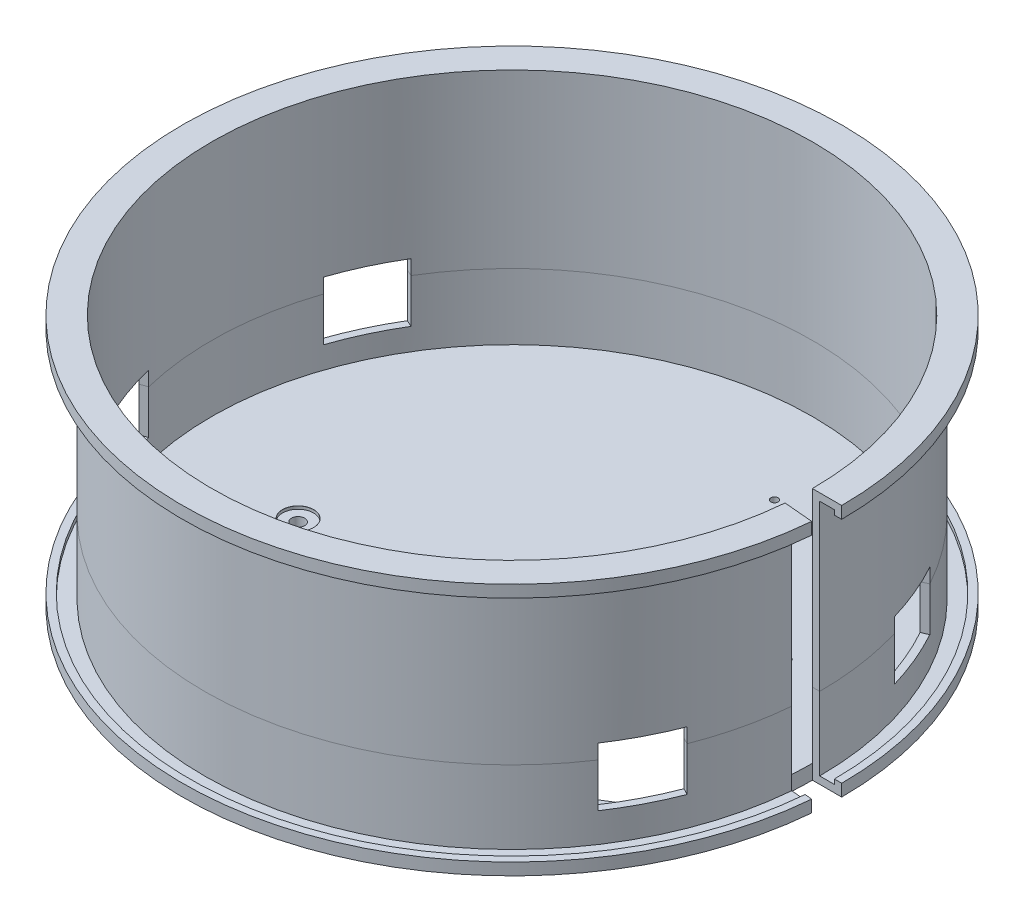
SolidWorks part; units mm, degrees
ref_plane "Front Plane" through (0, 0, 0) normal (0, 0, 1) x (1, 0, 0)
ref_plane "Top Plane" through (0, 0, 0) normal (0, 1, 0) x (1, 0, 0)
ref_plane "Right Plane" through (0, 0, 0) normal (1, 0, 0) x (0, 0, -1)
ref_axis "Axis1" through (0, 90.51, 0) along (0, -1, 0)
sketch "Sketch2" plane through (0, 0, 0) normal (0, 1, 0) x (1, 0, 0)
  circle A0 centre (0, 0) radius 102.5
  dimension "D1" = 102.5
extrude "Boss-Extrude1" add sketch "Sketch2" along normal blind 5
sketch "Sketch1" plane through (0, 0, 0) normal (0, 0, 1) x (1, 0, 0)
  line L0 (0, 82.2536) -> (0, -82.7575) construction
  line L1 (105, 2.5) -> (110, 2.5)
  line L2 (102.5, 0) -> (112.5, 0)
  line L3 (102.5, 0) -> (102.5, 86.2)
  line L4 (102.5, 86.2) -> (112.5, 86.2)
  line L5 (112.5, 0) -> (112.5, 86.2)
  line L6 (110, 2.5) -> (110, 83.7)
  line L7 (105, 83.7) -> (110, 83.7)
  line L8 (105, 2.5) -> (105, 83.7)
  line L9 (110, 82.1) -> (112.5, 82.1)
  line L10 (110, 4.1) -> (112.5, 4.1)
  line L11 (102.5, 43.1) -> (112.5, 43.1) construction
  dimension "D2" = 5
  dimension "D3" = 81.2
  dimension "D4" = 1.6
  dimension "D1" = 2.5
revolve "Revolve1" add sketch "Sketch1" angle 177.5 about L0 region at (104.6983, 43.1, 0) reverse direction yes
sketch "Sketch3" plane through (0, 0, 0) normal (0, 1, 0) x (1, 0, 0)
  line L0 (0, 0) -> (130, 0) construction
  line L1 (0, 0) -> (-119.4763, 5.2164) construction
  line L2 (-96.7219, 33.9283) -> (-88.2921, 52.0649)
  line L3 (90.32, 48.4619) -> (98.0115, 30)
  line L4 (0, 0) -> (92.9211, 90.9157) construction
  line L5 (0, 0) -> (2.8359, 129.9691) construction
  line L6 (0, 0) -> (-88.867, 94.8823) construction
  line L7 (0, 0) -> (-129.8763, 5.6705) construction
  line L8 (-129.8763, 5.6705) -> (-88.867, 94.8823)
  line L9 (-88.867, 94.8823) -> (2.8359, 129.9691)
  line L10 (2.8359, 129.9691) -> (92.9211, 90.9157)
  line L11 (92.9211, 90.9157) -> (130, 0)
  line L15 (0, 0) -> (-96.7984, -86.776) construction
  line L16 (-96.7984, -86.776) -> (-8.5024, -129.7217)
  line L17 (0, 0) -> (-8.5024, -129.7217) construction
  line L18 (-8.5024, -129.7217) -> (84.6437, -98.6683)
  line L19 (84.6437, -98.6683) -> (0, 0) construction
  line L20 (0, 0) -> (129.5053, -11.3302) construction
  line L21 (129.5053, -11.3302) -> (84.6437, -98.6683)
  line L22 (-129.8763, 5.6705) -> (-96.7984, -86.776)
  circle A0 centre (0, 0) radius 102.5 construction
  arc A1 (98.0115, 30) -> (90.32, 48.4619) centre (0, 0) ccw
  arc A2 (-102.4024, 4.471) -> (102.5, 0) centre (0, 0) ccw construction
  arc A3 (-96.7219, 33.9283) -> (-88.2921, 52.0649) centre (0, 0) cw
  circle A4 centre (0, 0) radius 130 construction
  dimension "D2" = 20
  dimension "D7" = 260
  dimension "D1" = 30
  dimension "D3" = 49.9691
  dimension "D4" = 30
  dimension "D5" = 20
  dimension "D6" = 177.5
ref_plane "Plane1" through (-92.507, 0, -42.9966) normal (0.9068, 0, 0.4215) x (0.4215, 0, -0.9068)
ref_plane "Plane2" through (94.1657, 0, -39.2309) normal (-0.9231, 0, 0.3846) x (0.3846, 0, 0.9231)
sketch "Sketch4" plane through (-92.507, 0, -42.9966) normal (0.9068, 0, 0.4215) x (0.4215, 0, -0.9068)
  line L0 (105, 2.5) -> (-40.061, 2.5) construction
  line L1 (105, 2.5) -> (-40.061, 2.5)
  line L3 (-11.25, 32.5) -> (11.25, 32.5)
  line L4 (-11.25, 32.5) -> (-11.25, 12.5)
  line L5 (-11.25, 12.5) -> (11.25, 12.5)
  line L6 (11.25, 32.5) -> (11.25, 12.5)
  line L7 (-11.25, 32.5) -> (11.25, 12.5) construction
  line L8 (-11.25, 12.5) -> (11.25, 32.5) construction
  line L9 (-10, 0) -> (10, 0) construction
  point P2 (0, 22.5)
  point P11 (0, 0)
  dimension "D1" = 10
  dimension "D2" = 20
  dimension "D3" = 22.5
extrude "Cut-Extrude1" cut sketch "Sketch4" against normal blind 10 and the other way blind 10 contours L6 L3 L4 L5 region at (-92.507, 22.5, -42.9966)
sketch "Sketch5" plane through (94.1657, 0, -39.2309) normal (-0.9231, 0, 0.3846) x (0.3846, 0, 0.9231)
  line L0 (40.3804, 2.5) -> (-105, 2.5) construction
  line L1 (40.3804, 2.5) -> (-105, 2.5)
  line L2 (-10, 0) -> (10, 0) construction
  line L3 (-11.25, 12.5) -> (11.25, 12.5)
  line L4 (-11.25, 12.5) -> (-11.25, 32.5)
  line L5 (-11.25, 32.5) -> (11.25, 32.5)
  line L6 (11.25, 12.5) -> (11.25, 32.5)
  line L7 (-11.25, 12.5) -> (11.25, 32.5) construction
  line L8 (-11.25, 32.5) -> (11.25, 12.5) construction
  point P2 (0, 22.5)
  point P9 (0, 0)
  dimension "D1" = 10
  dimension "D2" = 20
  dimension "D3" = 22.5
extrude "Cut-Extrude2" cut sketch "Sketch5" against normal blind 10 and the other way blind 10 contours L3 L6 L5 L4 region at (94.1657, 22.5, -39.2309)
move or copy body "Body-Move/Copy1" bodies to move or copy 104 copy yes number of copies 1 rotation origin (0, 0, 0) rotation axis (0, 1, 0) rotation angle 177.5
sketch "Sketch6" plane through (0, 0, 0) normal (0, -1, 0) x (1, 0, 0)
  line L7 (-81.1351, -32.0066) -> (-96.0687, -19.4497) construction
  line L9 (68.5462, 59.5076) -> (-1.549, -18.3411) construction
  line L10 (68.5462, 59.5076) -> (85.6386, 44.1176)
  line L11 (-7.1121, 60.6657) -> (-30.5635, 34.6203)
  line L12 (8.116, 40.2348) -> (-21.9488, 23.8618)
  line L13 (2.7739, 61.1838) -> (9.8337, 54.827)
  line L14 (-1.549, -18.3411) -> (-72.7256, -49.6124)
  line L15 (3.8496, 91.5208) -> (-96.0687, -19.4497)
  line L16 (68.5462, 59.5076) -> (31.389, 92.9641)
  line L17 (-81.1351, -32.0066) -> (18.3409, 78.4728) construction
  line L18 (-81.1351, -32.0066) -> (8.071, -1.2905) construction
  line L19 (-81.1351, -32.0066) -> (94.8761, 61.3488) construction
  line L20 (94.8761, 61.3488) -> (-81.1351, -32.0066) construction
  line L21 (-81.1351, -32.0066) -> (-17.4378, -16.1945) construction
  line L23 (16.9017, -71.4187) -> (68.94, -69.6015)
  line L24 (16.9017, -71.4187) -> (15.2174, -23.1881)
  line L25 (15.2174, -23.1881) -> (67.2557, -21.3709)
  line L26 (68.94, -69.6015) -> (67.2557, -21.3709)
  arc A11 (50.5662, -17.2493) -> (-1.549, -18.3411) centre (26.1216, -94.7886) ccw
  arc A12 (85.6386, 44.1176) -> (50.5662, -17.2493) centre (61.4397, 17.242) cw
  circle A13 centre (61.4397, 17.242) radius 33.75
  arc A14 (-21.9488, 23.8618) -> (-30.5635, 34.6203) centre (-25.2967, 30.0093) cw
  arc A15 (9.8337, 54.827) -> (8.116, 40.2348) centre (3.8116, 48.1387) cw
  arc A16 (2.7739, 61.1838) -> (-7.1121, 60.6657) centre (-1.9101, 55.9818) ccw
  circle A17 centre (-57.5971, 15.4314) radius 2
  circle A18 centre (9.8655, 30.5771) radius 2
  circle A19 centre (5.6358, 85.6586) radius 2
  arc A20 (-72.7256, -49.6124) -> (-96.0687, -19.4497) centre (-81.1351, -32.0066) cw
  arc A21 (31.389, 92.9641) -> (3.8496, 91.5208) centre (18.3409, 78.4728) ccw
  circle A22 centre (68.4081, -54.3707) radius 1.5
  circle A23 centre (67.433, -26.4478) radius 1.5
  circle A24 centre (15.2174, -23.1881) radius 1.5
  circle A25 centre (18.1709, -71.3744) radius 1.5
  dimension "D4" = 112
  dimension "D3" = 67.5
  dimension "D12" = 3
  dimension "D2" = 29
  dimension "D5" = 234
  dimension "D6" = 48.26
  dimension "D7" = 52.07
  dimension "D8" = 5.08
  dimension "D9" = 33.02
  dimension "D10" = 1.27
  dimension "D11" = 118.4
combine bodies "Combine1" operation type add bodies to combine 104 105
extrude "Cut-Extrude3" cut sketch "Sketch6" against normal blind 15 and the other way blind 5 contours L11 A14 L12 A15 L13 A16 | A13
sketch "Sketch7" plane through (0, 5, 0) normal (0, 1, 0) x (1, 0, 0)
  point P0 (5.6358, -85.6586)
  point P3 (-57.5971, -15.4314)
  point P6 (9.8655, -30.5771)
hole_wizard "Hole1" positions "Sketch7" profile "Sketch8" legacy end condition through all
sketch "Sketch8" plane through (5.6358, 5, 85.6586) normal (1, 0, 0) x (0, 0, 1)
  line L0 (0, 0) -> (0, 5)
  line L1 (0, 5) -> (2.25, 5)
  line L3 (2.25, 5) -> (2.25, 1)
  line L4 (5.295, 1) -> (2.25, 1)
  line L5 (5.295, 1) -> (5.295, 0.025)
  line L6 (5.295, 0.025) -> (5.32, 0)
  line L7 (5.32, 0) -> (0, 0)
  line L8 (-5.295, 0.025) -> (-5.32, 0) construction
  line L11 (0, -6.35) -> (0, 107.95) construction
  dimension "Thru Hole Dia." = 4.5
  dimension "Thru Hole Depth" = 5
  dimension "C'Bore Dia." = 10.59
  dimension "C'Bore Depth" = 1
  dimension "Near C'Sink Dia." = 10.64
  dimension "Near C'Sink Angle" = 90
sketch "Sketch9" plane through (0, 5, 0) normal (0, 1, 0) x (1, 0, 0)
  point P0 (15.2174, 23.1881)
  point P3 (67.433, 26.4478)
  point P6 (68.4081, 54.3707)
  point P9 (18.1709, 71.3744)
hole_wizard "M3x0.5 Tapped Hole1" positions "Sketch9" profile "Sketch11" tap size "M3x0.5" standard "ANSI Metric" end condition through all
sketch "Sketch11" plane through (15.2174, 5, -23.1881) normal (1, 0, 0) x (0, 0, 1)
  line L0 (0, 0) -> (0, 5)
  line L1 (0, 5) -> (1.25, 5)
  line L2 (1.25, 5) -> (1.25, 0)
  line L5 (1.25, 0) -> (0, 0)
  line L11 (0, -6.35) -> (0, 107.95) construction
  dimension "Thru Tap Drill Dia." = 2.5
  dimension "Thru Tap Drill Depth" = 5
cosmetic thread "Hole Thread1" parameters "D2"=3
cosmetic thread "Hole Thread2" parameters "D2"=3
cosmetic thread "Hole Thread3" parameters "D2"=3
cosmetic thread "Hole Thread4" parameters "D2"=3
ref_plane "Plane3" through (0, 27.5, 0) normal (0, -1, 0) x (-1, 0, 0)
split "Split1" trim tools "Plane3" bodies to split 109 resulting bodies 110 111
